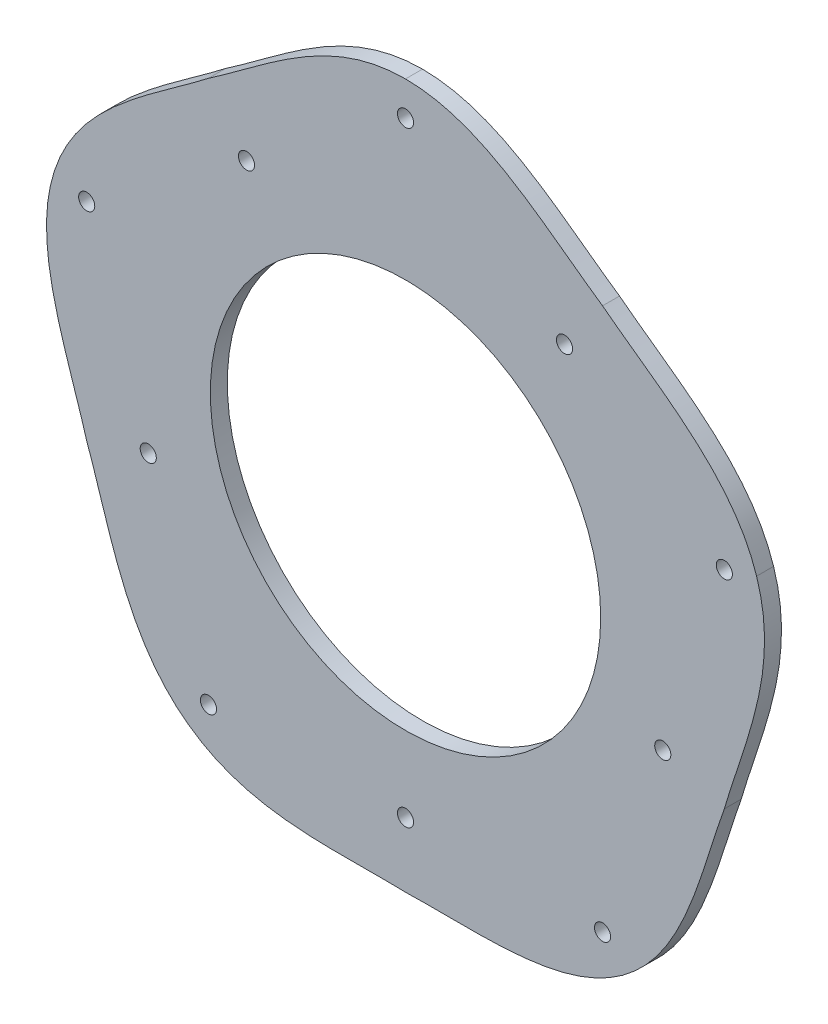
SolidWorks part; units mm, degrees
material "ABS"
ref_plane "Płaszczyzna przednia" through (0, 0, 0) normal (0, 0, 1) x (1, 0, 0)
ref_plane "Płaszczyzna górna" through (0, 0, 0) normal (0, 1, 0) x (1, 0, 0)
ref_plane "Płaszczyzna prawa" through (0, 0, 0) normal (1, 0, 0) x (0, 0, -1)
sketch "Szkic1" plane through (0, 0, 0) normal (0, 0, 1) x (1, 0, 0)
  line L0 (0, 0) -> (51.1373, 70.3845) construction
  line L1 (0, 0) -> (0, 87) construction
  circle A0 centre (0, 0) radius 79 construction
  circle A5 centre (0, 79) radius 1.9
  circle A9 centre (75.1335, 24.4123) radius 1.9
  circle A10 centre (46.435, -63.9123) radius 1.9
  circle A11 centre (-46.435, -63.9123) radius 1.9
  circle A12 centre (-75.1335, 24.4123) radius 1.9
  circle A13 centre (0, 0) radius 87 construction
  circle A54 centre (0, 0) radius 72.5
  circle A55 centre (0, 0) radius 46
  circle A56 centre (0, 0) radius 52
  circle A57 centre (0, 0) radius 68.5
  circle A59 centre (37.4713, 51.5748) radius 1.9
  circle A60 centre (0, 0) radius 63.75 construction
  circle A64 centre (60.6299, -19.6998) radius 1.9
  circle A65 centre (0, -63.75) radius 1.9
  circle A66 centre (-60.6299, -19.6998) radius 1.9
  circle A67 centre (-37.4713, 51.5748) radius 1.9
  spline S0 degree 3 poles (0, 87) (18.2248, 86.9986) (32.2889, 73.5369) (46.435, 63.9123) knots 0 0 0 0 1 1 1 1
  spline S1 degree 3 poles (82.7419, 26.8845) (77.1088, 44.2169) (59.9599, 53.4327) (46.435, 63.9123) knots 0 0 0 0 1 1 1 1
  spline S2 degree 3 poles (82.7419, 26.8845) (88.3724, 9.5512) (79.9156, -7.9844) (75.1335, -24.4123) knots 0 0 0 0 1 1 1 1
  spline S3 degree 3 poles (51.1373, -70.3845) (65.8807, -59.6711) (69.3462, -40.5137) (75.1335, -24.4123) knots 0 0 0 0 1 1 1 1
  spline S4 degree 3 poles (51.1373, -70.3845) (36.3923, -81.0957) (17.1016, -78.4715) (0, -79) knots 0 0 0 0 1 1 1 1
  spline S5 degree 3 poles (-51.1373, -70.3845) (-36.3923, -81.0957) (-17.1016, -78.4715) (0, -79) knots 0 0 0 0 1 1 1 1
  spline S6 degree 3 poles (-51.1373, -70.3845) (-65.8807, -59.6711) (-69.3462, -40.5137) (-75.1335, -24.4123) knots 0 0 0 0 1 1 1 1
  spline S7 degree 3 poles (-82.7419, 26.8845) (-88.3724, 9.5512) (-79.9156, -7.9844) (-75.1335, -24.4123) knots 0 0 0 0 1 1 1 1
  spline S8 degree 3 poles (-82.7419, 26.8845) (-77.1088, 44.2169) (-59.9599, 53.4327) (-46.435, 63.9123) knots 0 0 0 0 1 1 1 1
  spline S9 degree 3 poles (0, 87) (-18.2248, 86.9986) (-32.2889, 73.5369) (-46.435, 63.9123) knots 0 0 0 0 1 1 1 1
  point P13 (0, 0)
  point P18 (0, 0)
  point P27 (0, 0)
  point P64 (0, 0)
  point P69 (0, 0)
  point P188 (0, 0)
  dimension "D1" = 158
  dimension "D2" = 145
  dimension "D3" = 92
  dimension "D4" = 3.8
  dimension "D5" = 6
  dimension "D8" = 174
  dimension "D10" = 127.5
  dimension "D11" = 3.8
  dimension "D9" = 36
  dimension "D12" = 5
  dimension "D6" = 4
  dimension "D7" = 5
extrude "Dodanie-wyciągnięcie1" add sketch "Szkic1" along normal blind 4 contours S0 S9 S8 S7 S6 S5 S4 S3 S2 S1 A5 A54 A9 A10 A11 A12 | A56 A55 | A57 A56 | A54 A57 region at (-70.4494, 0, 0) region at (-50.5292, 0, 0) region at (-66.5625, 0, 0) region at (23.5794, 77.0008, 0)
